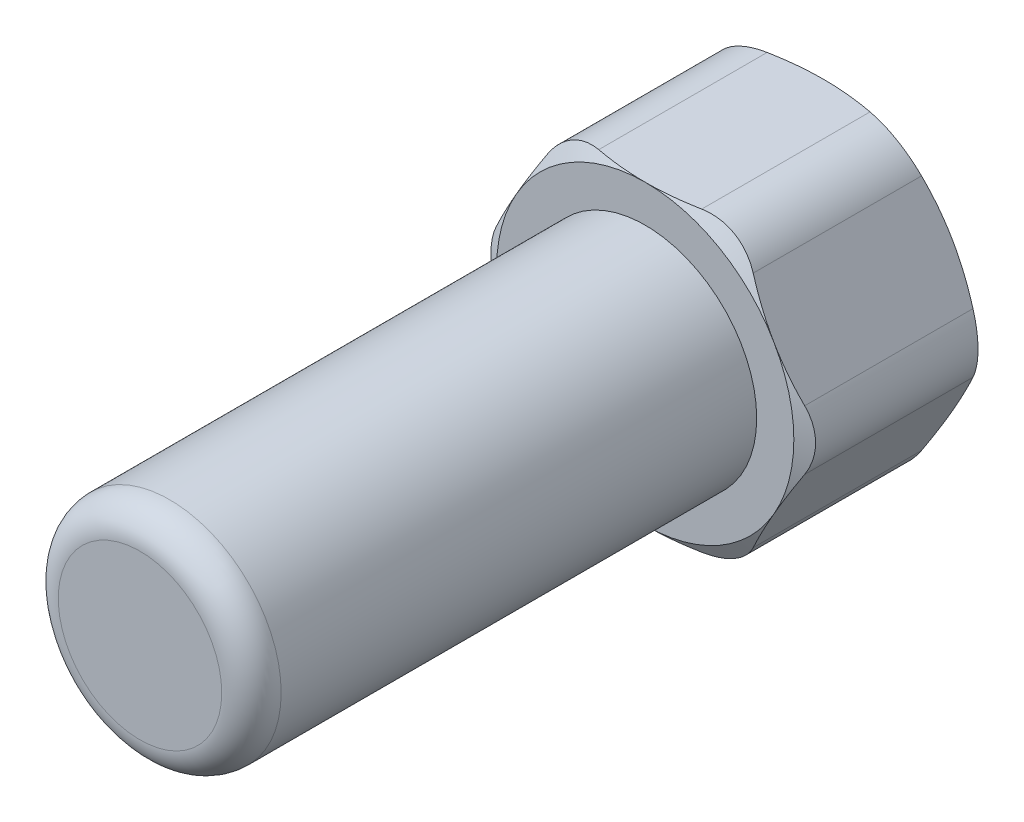
SolidWorks part; units mm, degrees
ref_plane "Front Plane" through (0, 0, 0) normal (0, 0, 1) x (1, 0, 0)
ref_plane "Top Plane" through (0, 0, 0) normal (0, 1, 0) x (1, 0, 0)
ref_plane "Right Plane" through (0, 0, 0) normal (1, 0, 0) x (0, 0, -1)
sketch "Sketch4" plane through (0, 0, 0) normal (0, 0, 1) x (1, 0, 0)
  line L1 (-1.4434, 2.5) -> (-2.8868, 0)
  line L2 (-2.8868, 0) -> (-1.4434, -2.5)
  line L3 (-1.4434, -2.5) -> (1.4434, -2.5)
  line L4 (1.4434, -2.5) -> (2.8868, 0)
  line L5 (2.8868, 0) -> (1.4434, 2.5)
  line L6 (1.4434, 2.5) -> (-1.4434, 2.5)
  circle A0 centre (0, 0) radius 2.5 construction
  circle A1 centre (0, 0) radius 1.875
  dimension "D1" = 3.75
  dimension "D2" = 5
extrude "Boss-Extrude2" add sketch "Sketch4" along normal mid plane 3 contours A1 | L5 L6 L1 L2 L3 L4 A1 region at (0, 2.4236, 0) region at (0, 0, 0)
sketch "Sketch5" plane through (0, 0, 1.5) normal (0, 0, 1) x (1, 0, 0)
  circle A0 centre (0, 0) radius 2.5 construction
  circle A1 centre (0, 0) radius 2.5
extrude "Cut-Extrude1" cut sketch "Sketch5" against normal blind 15 draft 60 flip side to cut
mirror "Mirror1" about plane through (0, 0, 0) normal (0, 0, 1) of "Cut-Extrude1"
extrude "Boss-Extrude3" add sketch "Sketch4<3>" along normal blind 10 contours A1
sketch "Sketch4<3>" plane through (0, 0, 0) normal (0, 0, 1) x (1, 0, 0) same geometry as "Sketch4"
fillet "Fillet1" radius 1 6 edges at (2.8868, 0, 0) (1.4434, -2.5, 0) (-1.4434, -2.5, 0) (-2.8868, 0, 0) (-1.4434, 2.5, 0) (1.4434, 2.5, 0)
fillet "Fillet2" radius 0.5 1 edges at (1.875, 0, 10)
